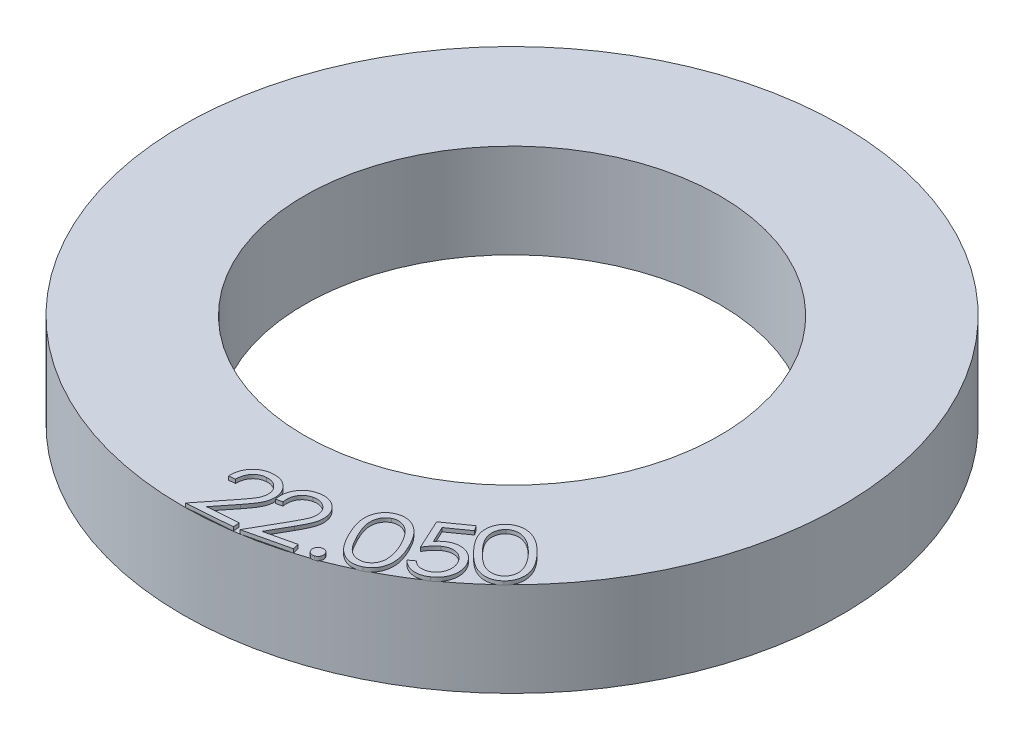
SolidWorks part; units mm, degrees
ref_plane "Front Plane" through (0, 0, 0) normal (0, 0, 1) x (1, 0, 0)
ref_plane "Top Plane" through (0, 0, 0) normal (0, 1, 0) x (1, 0, 0)
ref_plane "Right Plane" through (0, 0, 0) normal (1, 0, 0) x (0, 0, -1)
ref_axis "X" through (-88.99, 0, 0) along (1, 0, 0)
ref_axis "Y" through (0, 55, 0) along (0, -1, 0)
ref_axis "Z" through (0, 0, -88.99) along (0, 0, 1)
sketch "Sketch1" plane through (0, 0, 0) normal (0, 1, 0) x (1, 0, 0)
  circle A0 centre (0, 0) radius 17.5
  circle A1 centre (0, 0) radius 11.025
  dimension "D1" = 35
  dimension "D2" = 22.05
extrude "Boss-Extrude1" add sketch "Sketch1" along normal blind 5
sketch "Sketch3" plane through (0, 5, 0) normal (0, 1, 0) x (1, 0, 0)
  text T0 "22.050"
extrude "Boss-Extrude3" add sketch "Sketch3" along normal blind 0.2
